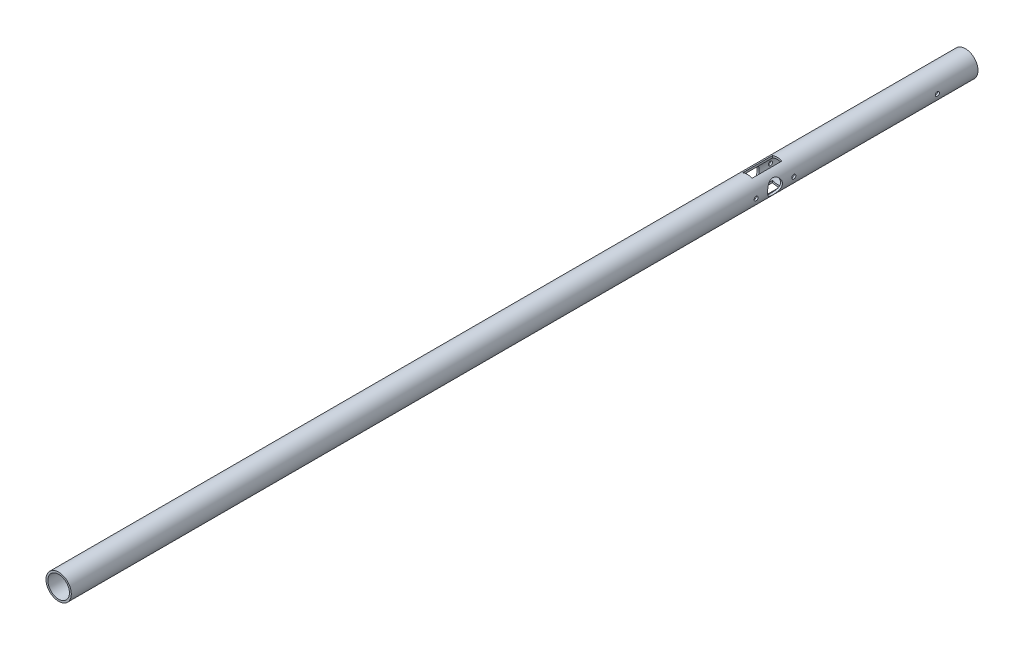
SolidWorks part; units mm, degrees
material "6061-T4 (SS)"
ref_plane "Front" through (0, 0, 0) normal (0, 0, 1) x (1, 0, 0)
ref_plane "Top" through (0, 0, 0) normal (0, 1, 0) x (1, 0, 0)
ref_plane "Right" through (0, 0, 0) normal (1, 0, 0) x (0, 0, -1)
sketch "Sketch1" plane through (0, 0, 0) normal (0, 0, 1) x (1, 0, 0)
  circle A0 centre (0, 0) radius 9.36
  circle A1 centre (0, 0) radius 7.99
extrude "Extrude1" add sketch "Sketch1" along normal blind 670
sketch "Sketch2" plane through (0, 0, 0) normal (1, 0, 0) x (0, 0, -1)
  line L0 (-30, -47.5362) -> (-30, 39.1475) construction
  line L1 (0, -9.36) -> (0, 9.36) construction
  line L2 (-150, -93.5027) -> (-150, 51.4365) construction
  line L3 (-670, 9.36) -> (-670, -9.36) construction
  circle A0 centre (-30, 0) radius 1.5
  circle A1 centre (-150, 0) radius 5.5
  circle A2 centre (-136.0625, 0) radius 1.5
  circle A3 centre (-163.9375, 0) radius 1.5
  point P10 (-163.9375, 0)
  point P11 (-136.0625, 0)
  point P16 (-670, 0)
  dimension "D2" = 150
  dimension "D3" = 13.9375
  dimension "D5" = 506.0625
  dimension "D1" = 30
  dimension "D4" = 13.9375
extrude "Extrude2" cut sketch "Sketch2" against normal through all and the other way through all
sketch "Sketch3" plane through (0, 0, 0) normal (0, 1, 0) x (1, 0, 0)
  line L0 (-54.8402, -150) -> (72.4613, -150) construction
  line L1 (7.99, 0) -> (-7.99, 0) construction
  line L2 (-44.3384, -139) -> (38.4408, -139) construction
  line L3 (-76.6388, -161) -> (67.6466, -161) construction
  line L4 (3.5, -160.8387) -> (3.5, -87.3966) construction
  line L5 (0, -179.9469) -> (0, -88.7091) construction
  line L6 (-3.5, -169.4108) -> (-3.5, -98.3485) construction
  line L8 (-3.5, -139) -> (3.5, -139)
  line L9 (-3.5, -139) -> (-3.5, -161)
  line L10 (-3.5, -161) -> (3.5, -161)
  line L11 (3.5, -139) -> (3.5, -161)
  dimension "D1" = 150
  dimension "D2" = 11
  dimension "D3" = 22
  dimension "D4" = 3.5
  dimension "D5" = 7
extrude "Extrude3" cut sketch "Sketch3" against normal blind 25 and the other way blind 25
